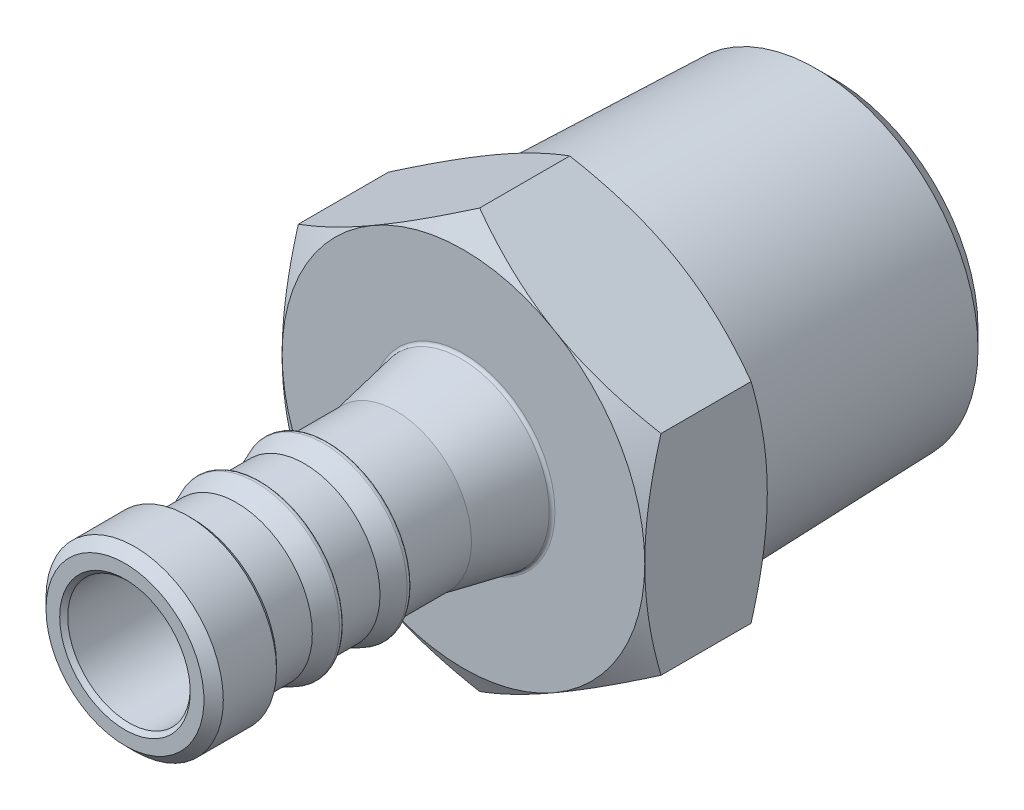
SolidWorks part; units mm, degrees
material "Alloy Steel"
ref_plane "Front Plane" through (0, 0, 0) normal (0, 0, 1) x (1, 0, 0)
ref_plane "Top Plane" through (0, 0, 0) normal (0, 1, 0) x (1, 0, 0)
ref_plane "Right Plane" through (0, 0, 0) normal (1, 0, 0) x (0, 0, -1)
sketch "Sketch1" plane through (0, 0, 0) normal (1, 0, 0) x (0, 0, -1)
  line L0 (-26.67, 0) -> (0, 0) construction
  line L1 (0, 0) -> (9.652, 0) construction
  line L2 (9.652, 0) -> (29.21, 0) construction
  line L3 (-26.67, 6.35) -> (-26.67, -6.35) construction
  line L5 (0, 14.2875) -> (0, -14.2875) construction
  line L6 (-26.67, 4.826) -> (-26.67, -4.826) construction
  line L7 (-26.67, 6.985) -> (-26.67, -6.985) construction
  line L8 (9.652, 14.2875) -> (9.652, -14.2875) construction
  line L9 (29.21, 6.4135) -> (29.21, -6.4135) construction
  line L10 (9.0551, -13.335) -> (9.0551, 13.335) construction
  line L11 (9.0551, 13.335) -> (29.21, 12.7075) construction
  line L12 (29.21, 12.7075) -> (29.21, -12.7075) construction
  line L13 (9.0551, 13.335) -> (10.8694, 13.335) construction
  point P26 (9.0551, 0)
sketch "Sketch2" plane through (0, 0, 0) normal (1, 0, 0) x (0, 0, -1)
  line L1 (-21.082, 5.969) -> (-17.8771, 5.969)
  line L2 (0, 7.2152) -> (0, 0)
  line L3 (0, 14.2875) -> (0, -14.2875) construction
  line L4 (-26.67, 0) -> (0, 0)
  line L7 (-26.67, 0) -> (-26.67, 6.985)
  line L9 (-26.67, 0) -> (0, 0) construction
  line L14 (-21.336, 6.223) -> (-21.336, 6.985)
  line L15 (-21.336, 6.985) -> (-26.67, 6.985)
  line L18 (-26.67, 14.2875) -> (-21.336, 14.2875) construction
  line L19 (-21.336, 14.2875) -> (-16.002, 14.2875) construction
  line L20 (-16.002, 14.2875) -> (-10.668, 14.2875) construction
  line L21 (-10.668, 14.2875) -> (-5.334, 14.2875) construction
  line L22 (-5.334, 14.2875) -> (0, 14.2875) construction
  line L23 (-26.67, 0) -> (-26.67, 14.2875) construction
  line L24 (-17.8771, 5.969) -> (-16.3512, 6.5855)
  line L25 (-16.002, 6.35) -> (-16.002, 6.223)
  line L26 (-15.748, 5.969) -> (-12.5431, 5.969)
  line L27 (-12.5431, 5.969) -> (-11.0172, 6.5855)
  line L28 (-10.668, 6.35) -> (-10.668, 6.223)
  line L29 (-10.414, 5.969) -> (-5.334, 5.969)
  line L30 (-5.334, 5.969) -> (-0.2055, 6.9659)
  line L38 (-16.256, 6.604) -> (-10.922, 6.604) construction
  arc A0 (-16.3512, 6.5855) -> (-16.002, 6.35) centre (-16.256, 6.35) cw
  arc A1 (-16.002, 6.223) -> (-15.748, 5.969) centre (-15.748, 6.223) ccw
  arc A2 (-11.0172, 6.5855) -> (-10.668, 6.35) centre (-10.922, 6.35) cw
  arc A3 (-10.668, 6.223) -> (-10.414, 5.969) centre (-10.414, 6.223) ccw
  arc A8 (-21.336, 6.223) -> (-21.082, 5.969) centre (-21.082, 6.223) ccw
  arc A10 (-0.2055, 6.9659) -> (0, 7.2152) centre (-0.254, 7.2152) ccw
  point P39 (-16.002, 5.969)
  point P44 (-10.668, 5.969)
  point P66 (-21.336, 5.969)
  dimension "D2" = 0.254
  dimension "D5" = 0.254
  dimension "D6" = 0.254
  dimension "D1" = 22
  dimension "D3" = 1.016
  dimension "D4" = 11
  dimension "D7" = 0.635
revolve "Revolve1" add sketch "Sketch2" angle 360 about L9
chamfer "Chamfer1" distance 0.381 angle 45 1 edges at (6.985, 0, 21.336)
chamfer "Chamfer2" distance 0.762 angle 45 1 edges at (6.985, 0, 26.67)
ref_plane "Plane1" through (0, 0, -29.21) normal (0, 0, 1) x (1, 0, 0)
sketch "Sketch3" plane through (0, 0, -29.21) normal (0, 0, 1) x (1, 0, 0)
  circle A0 centre (0, 0) radius 12.7075
extrude "Boss-Extrude1" add sketch "Sketch3" along normal up to vertex (19.558 mm away) draft 1.783 separate body up to point (0, 0, -9.652) draft outward yes
sketch "Sketch4" plane through (0, 0, -29.21) normal (0, 0, -1) x (-1, 0, 0)
  circle A1 centre (0, 0) radius 12.7075
  circle A2 centre (0, 0) radius 12.7075
  point P0 (0, 12.7075)
  dimension "D1" = 0
curve "Helix/Spiral1" [suppressed]
sketch "Sketch5" plane through (0, 0, 0) normal (1, 0, 0) x (0, 0, -1)
  line L0 (29.0966, 12.9039) -> (30.9109, 12.9039) construction
  line L1 (30.9109, 12.9039) -> (30.0038, 11.3327) construction
  line L2 (30.0038, 11.3327) -> (29.0966, 12.9039) construction
  line L3 (29.8904, 11.5291) -> (30.1171, 11.5291) construction
  line L4 (29.21, 12.7075) -> (30.7975, 12.7075) construction
  line L5 (30.0038, 11.3327) -> (30.0038, 11.5291) construction
  line L6 (30.0038, 12.7075) -> (30.0038, 12.9039) construction
  line L7 (30.0038, 12.8057) -> (30.8542, 12.8057) construction
  line L8 (30.8542, 12.8057) -> (29.0966, 12.9039)
  line L9 (29.0966, 12.9039) -> (29.8904, 11.5291)
  line L10 (29.8904, 11.5291) -> (30.1171, 11.5291)
  line L11 (30.1171, 11.5291) -> (30.8542, 12.8057)
  line L12 (30.0038, 11.3327) -> (30.0038, -12.6828) construction
  line L13 (30.0038, -12.6828) -> (28.1903, -12.7392) construction
  line L14 (28.1903, -12.7392) -> (26.3769, -12.7957) construction
  line L15 (26.3769, -12.7957) -> (24.5635, -12.8521) construction
  line L16 (24.5635, -12.8521) -> (22.7501, -12.9086) construction
  line L17 (9.652, -13.3164) -> (29.21, -12.7075) construction
  dimension "D1" = 1.8143
  dimension "D2" = 0.2268
sweep "Cut-Sweep1" [suppressed] cut profiles "Sketch5" path "Helix/Spiral1"
sketch "Sketch6" plane through (0, 0, -29.21) normal (0, 0, -1) x (-1, 0, 0)
  circle A0 centre (0, 0) radius 11.3327
extrude "Cut-Extrude1" cut sketch "Sketch6" against normal up to vertex (19.558 mm away) draft 45 flip side to cut up to point (0, 0, -9.652)
sketch "Sketch7" plane through (0, 0, 0) normal (0, 0, -1) x (-1, 0, 0)
  line L1 (0, 16.4978) -> (-14.2875, 8.2489)
  line L2 (-14.2875, 8.2489) -> (-14.2875, -8.2489)
  line L3 (-14.2875, -8.2489) -> (0, -16.4978)
  line L4 (0, -16.4978) -> (14.2875, -8.2489)
  line L5 (14.2875, -8.2489) -> (14.2875, 8.2489)
  line L6 (14.2875, 8.2489) -> (0, 16.4978)
  circle A0 centre (0, 0) radius 14.2875 construction
extrude "Boss-Extrude2" add sketch "Sketch7" along normal up to vertex (9.652 mm away) up to point (0, 0, -9.652)
sketch "Sketch8" plane through (0, 0, 0) normal (0, 0, 1) x (1, 0, 0)
  circle A0 centre (0, 0) radius 14.2875 construction
  circle A1 centre (0, 0) radius 14.2875
extrude "Cut-Extrude2" cut sketch "Sketch8" against normal up to vertex (9.652 mm away) draft 60 flip side to cut up to point (0, 0, -9.652)
sketch "Sketch9" plane through (0, 0, -9.652) normal (0, 0, -1) x (-1, 0, 0)
  circle A1 centre (0, 0) radius 14.2875
  circle A2 centre (0, 0) radius 14.2875
  dimension "D1" = 0
extrude "Cut-Extrude3" cut sketch "Sketch9" against normal up to vertex (9.652 mm away) draft 60 flip side to cut up to point (0, 0, 0)
sketch "Sketch10" plane through (0, 0, 0) normal (1, 0, 0) x (0, 0, -1)
  line L0 (0, 0) -> (-26.67, 0) construction
  line L1 (-26.67, 4.826) -> (9.652, 4.826)
  line L2 (-26.67, 4.826) -> (-26.67, 0)
  line L3 (-26.67, 0) -> (9.652, 0)
  line L4 (9.652, 4.826) -> (9.652, 0)
revolve "Cut-Revolve1" cut sketch "Sketch10" angle 360 about L0
chamfer "Chamfer3" distance 0.3175 angle 45 1 edges at (-4.826, 0, 26.67)
sketch "Sketch11" plane through (0, 0, 0) normal (1, 0, 0) x (0, 0, -1)
  line L0 (0, 0) -> (29.21, 0) construction
  line L1 (0, 14.2875) -> (0, -14.2875) construction
  line L2 (29.21, 0) -> (29.21, 6.4135)
  line L3 (29.21, 6.4135) -> (9.652, 6.4135)
  line L4 (9.652, 6.4135) -> (5.7984, 0)
  line L5 (5.7984, 0) -> (29.21, 0)
  line L6 (9.652, 14.2875) -> (9.652, -14.2875) construction
  dimension "D1" = 59
revolve "Cut-Revolve2" cut sketch "Sketch11" angle 360 about L0
chamfer "Chamfer4" distance 0.508 angle 45 1 edges at (6.4135, 0, -29.21)
equation "\"D3@Boss-Extrude1\" = \"Taper@Sketch1\""
equation "\"D6@Helix/Spiral1\" = \"Taper@Sketch1\""
equation "\"D4@Helix/Spiral1\" = \"Pitch@Sketch1\""
equation "\"D3@Helix/Spiral1\" = \"D4@Helix/Spiral1\" + \"L4@Sketch1\""
equation "\"D1@Sketch5\" = \"D4@Helix/Spiral1\""
equation "\"D2@Sketch5\" = \"D1@Sketch5\" / 8"
